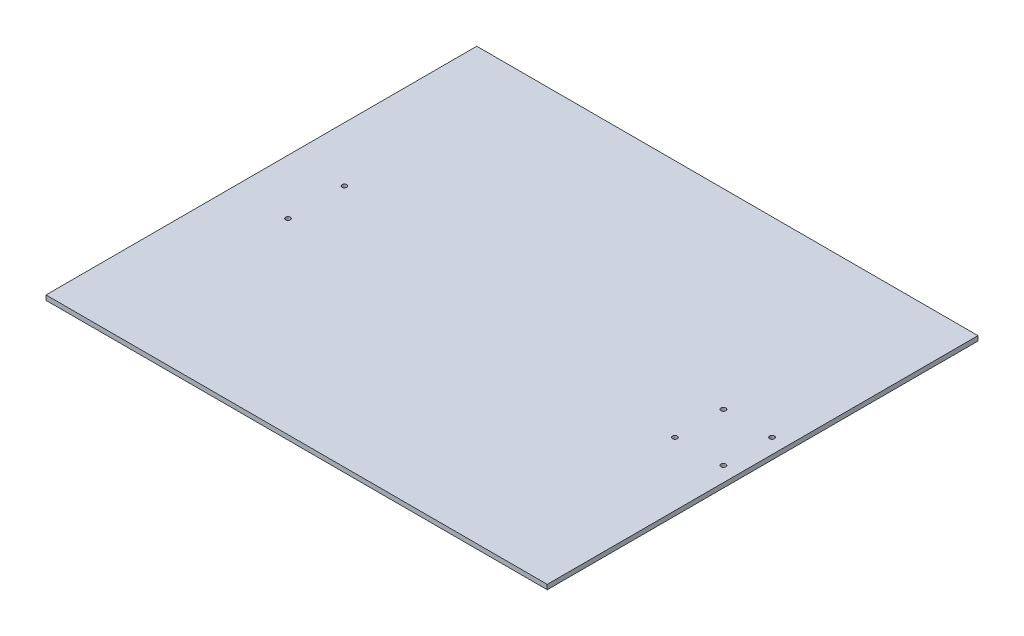
SolidWorks part; units mm, degrees
material "Acrílico (Impacto medio-alto)"
ref_plane "Alzado" through (0, 0, 0) normal (0, 0, 1) x (1, 0, 0)
ref_plane "Planta" through (0, 0, 0) normal (0, 1, 0) x (1, 0, 0)
ref_plane "Vista lateral" through (0, 0, 0) normal (1, 0, 0) x (0, 0, -1)
sketch "Sketch1" plane through (0, 0, 0) normal (0, 1, 0) x (1, 0, 0)
  line L1 (-160, -137.5) -> (160, -137.5)
  line L2 (-160, -137.5) -> (-160, 137.5)
  line L3 (-160, 137.5) -> (160, 137.5)
  line L4 (160, -137.5) -> (160, 137.5)
  line L5 (-160, -137.5) -> (160, 137.5) construction
  line L6 (-160, 137.5) -> (160, -137.5) construction
  point P0 (0, 0)
  dimension "D1" = 320
  dimension "D2" = 275
extrude "Boss-Extrude1" add sketch "Sketch1" along normal blind 3
sketch "Sketch2" plane through (0, 3, 0) normal (0, 1, 0) x (1, 0, 0)
  line L0 (0, 0) -> (160, 0) construction
  line L1 (160, -137.5) -> (160, 137.5) construction
  line L3 (119.5, -15.5) -> (150.5, -15.5)
  line L4 (119.5, -15.5) -> (119.5, 15.5)
  line L5 (119.5, 15.5) -> (150.5, 15.5)
  line L6 (150.5, -15.5) -> (150.5, 15.5)
  line L7 (119.5, -15.5) -> (150.5, 15.5) construction
  line L8 (119.5, 15.5) -> (150.5, -15.5) construction
  point P5 (135, 0)
  dimension "D1" = 31
  dimension "D2" = 31
  dimension "D3" = 25
sketch "Sketch3" plane through (0, 3, 0) normal (0, 1, 0) x (1, 0, 0)
  point P0 (150.5, 15.5)
  point P3 (150.5, -15.5)
  point P6 (119.5, -15.5)
  point P9 (119.5, 15.5)
hole_wizard "Taladro de margen para M2.51" positions "Sketch3" profile "Sketch4" hole size "M2.5" standard "ISO" end condition through all
sketch "Sketch4" plane through (150.5, 3, -15.5) normal (1, 0, 0) x (0, 0, 1)
  line L0 (0, 0) -> (0, 3)
  line L1 (0, 3) -> (1.55, 3)
  line L2 (1.55, 3) -> (1.55, 0)
  line L5 (1.55, 0) -> (0, 0)
  line L11 (0, -6.35) -> (0, 107.95) construction
  dimension "Diámetro de taladro hasta el siguiente" = 3.1
  dimension "Profundidad de taladro hasta el siguiente" = 3
sketch "Sketch6" plane through (0, 3, 0) normal (0, 1, 0) x (1, 0, 0)
  line L0 (0, 0) -> (-160, 0) construction
  line L1 (-160, 137.5) -> (-160, -137.5) construction
  line L2 (-125, 0) -> (-125, 18) construction
  line L3 (-125, 0) -> (-125, -18) construction
  circle A0 centre (-125, -18) radius 1.5
  circle A1 centre (-125, 18) radius 1.5
  dimension "D2" = 3
  dimension "D3" = 3
  dimension "D1" = 36
  dimension "D4" = 35
extrude "Cut-Extrude1" cut sketch "Sketch6" against normal through all
